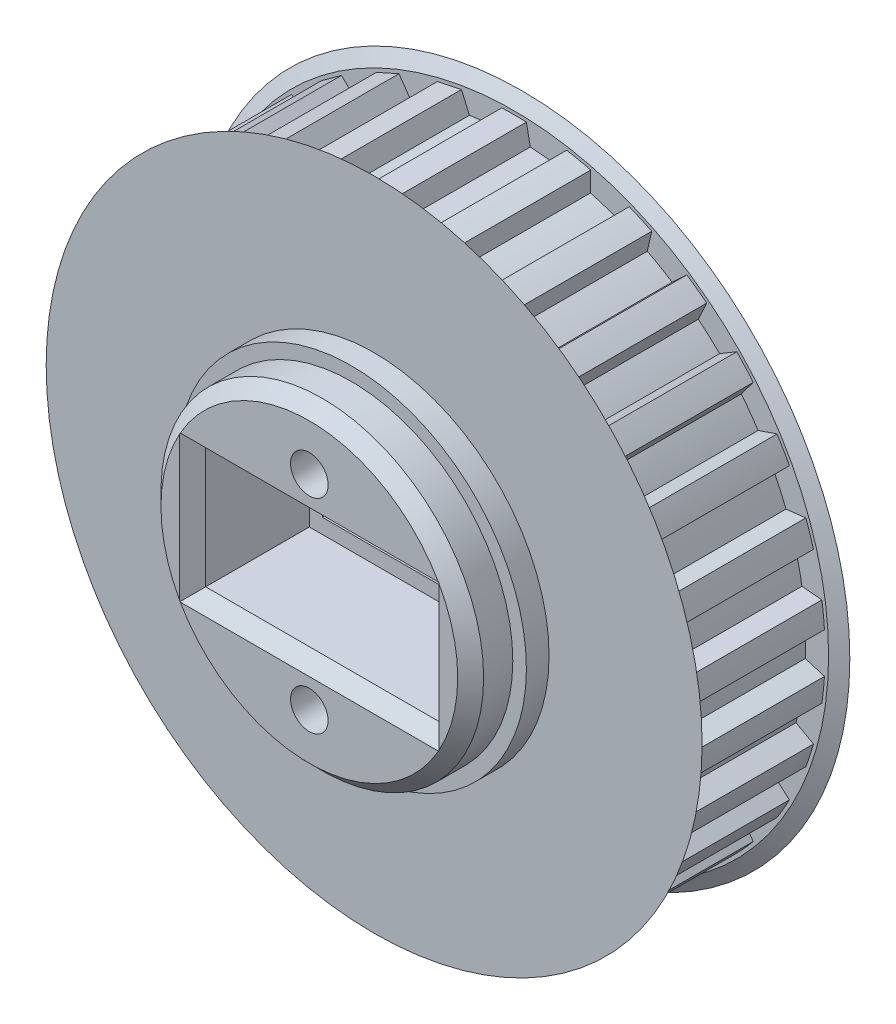
SolidWorks part; units mm, degrees
material "ABS"
ref_plane "Alzado" through (0, 0, 0) normal (0, 0, 1) x (1, 0, 0)
ref_plane "Planta" through (0, 0, 0) normal (0, 1, 0) x (1, 0, 0)
ref_plane "Vista lateral" through (0, 0, 0) normal (1, 0, 0) x (0, 0, -1)
sketch "Croquis1" plane through (0, 0, 0) normal (0, 0, 1) x (1, 0, 0)
  line L0 (0, 0) -> (0, 14.5885) construction
  line L1 (-0.95, 23.9812) -> (-1.25, 22.4653)
  line L2 (0.95, 23.9812) -> (1.25, 22.4653)
  line L3 (5.9152, 23.2596) -> (5.8935, 21.7144)
  line L4 (4.0567, 23.6547) -> (3.4481, 22.2342)
  line L5 (10.6219, 21.5215) -> (10.2794, 20.0146)
  line L6 (8.8862, 22.2943) -> (7.9955, 21.0314)
  line L7 (14.8644, 18.8428) -> (14.216, 17.44)
  line L8 (13.3272, 19.9596) -> (12.1935, 18.9095)
  line L9 (18.4572, 15.3406) -> (17.5313, 14.1033)
  line L10 (17.1858, 16.7525) -> (15.8585, 15.9611)
  line L11 (21.2433, 11.1679) -> (20.0805, 10.1501)
  line L12 (20.2933, 12.8133) -> (18.8305, 12.3152)
  line L13 (23.101, 6.5071) -> (21.752, 5.7533)
  line L14 (22.5139, 8.3141) -> (20.9795, 8.131)
  line L15 (23.9491, 1.5619) -> (22.4728, 1.1051)
  line L16 (23.7505, 3.4515) -> (22.2115, 3.5914)
  line L17 (23.7505, -3.4515) -> (22.2115, -3.5914)
  line L18 (23.9491, -1.5619) -> (22.4728, -1.1051)
  line L19 (22.5139, -8.3141) -> (20.9795, -8.131)
  line L20 (23.101, -6.5071) -> (21.752, -5.7533)
  line L21 (20.2933, -12.8133) -> (18.8305, -12.3152)
  line L22 (21.2433, -11.1679) -> (20.0805, -10.1501)
  line L23 (17.1858, -16.7525) -> (15.8585, -15.9611)
  line L24 (18.4572, -15.3406) -> (17.5313, -14.1033)
  line L25 (13.3272, -19.9596) -> (12.1935, -18.9095)
  line L26 (14.8644, -18.8428) -> (14.216, -17.44)
  line L27 (8.8862, -22.2943) -> (7.9955, -21.0314)
  line L28 (10.6219, -21.5215) -> (10.2794, -20.0146)
  line L29 (4.0567, -23.6547) -> (3.4481, -22.2342)
  line L30 (5.9152, -23.2596) -> (5.8935, -21.7144)
  line L31 (-0.95, -23.9812) -> (-1.25, -22.4653)
  line L32 (0.95, -23.9812) -> (1.25, -22.4653)
  line L33 (-5.9152, -23.2596) -> (-5.8935, -21.7144)
  line L34 (-4.0567, -23.6547) -> (-3.4481, -22.2342)
  line L35 (-10.6219, -21.5215) -> (-10.2794, -20.0146)
  line L36 (-8.8862, -22.2943) -> (-7.9955, -21.0314)
  line L37 (-14.8644, -18.8428) -> (-14.216, -17.44)
  line L38 (-13.3272, -19.9596) -> (-12.1935, -18.9095)
  line L39 (-18.4572, -15.3406) -> (-17.5313, -14.1033)
  line L40 (-17.1858, -16.7525) -> (-15.8585, -15.9611)
  line L41 (-21.2433, -11.1679) -> (-20.0805, -10.1501)
  line L42 (-20.2933, -12.8133) -> (-18.8305, -12.3152)
  line L43 (-23.101, -6.5071) -> (-21.752, -5.7533)
  line L44 (-22.5139, -8.3141) -> (-20.9795, -8.131)
  line L45 (-23.9491, -1.5619) -> (-22.4728, -1.1051)
  line L46 (-23.7505, -3.4515) -> (-22.2115, -3.5914)
  line L47 (-23.7505, 3.4515) -> (-22.2115, 3.5914)
  line L48 (-23.9491, 1.5619) -> (-22.4728, 1.1051)
  line L49 (-22.5139, 8.3141) -> (-20.9795, 8.131)
  line L50 (-23.101, 6.5071) -> (-21.752, 5.7533)
  line L51 (-20.2933, 12.8133) -> (-18.8305, 12.3152)
  line L52 (-21.2433, 11.1679) -> (-20.0805, 10.1501)
  line L53 (-17.1858, 16.7525) -> (-15.8585, 15.9611)
  line L54 (-18.4572, 15.3406) -> (-17.5313, 14.1033)
  line L55 (-13.3272, 19.9596) -> (-12.1935, 18.9095)
  line L56 (-14.8644, 18.8428) -> (-14.216, 17.44)
  line L57 (-18.4572, 15.3406) -> (-17.1858, 16.7525)
  line L58 (-14.8644, 18.8428) -> (-13.3272, 19.9596)
  line L59 (-8.8862, 22.2943) -> (-7.9955, 21.0314)
  line L60 (-10.6219, 21.5215) -> (-10.2794, 20.0146)
  line L61 (-4.0567, 23.6547) -> (-3.4481, 22.2342)
  line L62 (-5.9152, 23.2596) -> (-5.8935, 21.7144)
  line L63 (-10.6219, 21.5215) -> (-8.8862, 22.2943)
  line L64 (-5.9152, 23.2596) -> (-4.0567, 23.6547)
  arc A0 (-17.5313, 14.1033) -> (-18.8305, 12.3152) centre (0, 0) ccw
  arc A1 (3.4481, 22.2342) -> (1.25, 22.4653) centre (0, 0) ccw
  arc A2 (-14.216, 17.44) -> (-15.8585, 15.9611) centre (0, 0) ccw
  arc A3 (-5.8935, 21.7144) -> (-7.9955, 21.0314) centre (0, 0) ccw
  arc A4 (-10.2794, 20.0146) -> (-12.1935, 18.9095) centre (0, 0) ccw
  arc A8 (-20.2933, 12.8133) -> (-21.2433, 11.1679) centre (0, 0) ccw
  arc A9 (-22.5139, 8.3141) -> (-23.101, 6.5071) centre (0, 0) ccw
  arc A10 (-23.7505, 3.4515) -> (-23.9491, 1.5619) centre (0, 0) ccw
  arc A11 (5.9152, 23.2596) -> (4.0567, 23.6547) centre (0, 0) ccw
  arc A12 (0.95, 23.9812) -> (-0.95, 23.9812) centre (0, 0) ccw
  arc A16 (10.6219, 21.5215) -> (8.8862, 22.2943) centre (0, 0) ccw
  arc A17 (14.8644, 18.8428) -> (13.3272, 19.9596) centre (0, 0) ccw
  arc A18 (18.4572, 15.3406) -> (17.1858, 16.7525) centre (0, 0) ccw
  arc A19 (21.2433, 11.1679) -> (20.2933, 12.8133) centre (0, 0) ccw
  arc A20 (23.101, 6.5071) -> (22.5139, 8.3141) centre (0, 0) ccw
  arc A21 (23.9491, 1.5619) -> (23.7505, 3.4515) centre (0, 0) ccw
  arc A22 (23.7505, -3.4515) -> (23.9491, -1.5619) centre (0, 0) ccw
  arc A23 (22.5139, -8.3141) -> (23.101, -6.5071) centre (0, 0) ccw
  arc A24 (20.2933, -12.8133) -> (21.2433, -11.1679) centre (0, 0) ccw
  arc A25 (17.1858, -16.7525) -> (18.4572, -15.3406) centre (0, 0) ccw
  arc A26 (-0.95, -23.9812) -> (0.95, -23.9812) centre (0, 0) ccw
  arc A27 (-5.9152, -23.2596) -> (-4.0567, -23.6547) centre (0, 0) ccw
  arc A28 (-10.6219, -21.5215) -> (-8.8862, -22.2943) centre (0, 0) ccw
  arc A29 (-18.4572, -15.3406) -> (-17.1858, -16.7525) centre (0, 0) ccw
  arc A30 (-21.2433, -11.1679) -> (-20.2933, -12.8133) centre (0, 0) ccw
  arc A31 (-23.101, -6.5071) -> (-22.5139, -8.3141) centre (0, 0) ccw
  arc A32 (-23.9491, -1.5619) -> (-23.7505, -3.4515) centre (0, 0) ccw
  arc A33 (4.0567, -23.6547) -> (5.9152, -23.2596) centre (0, 0) ccw
  arc A34 (8.8862, -22.2943) -> (10.6219, -21.5215) centre (0, 0) ccw
  arc A35 (13.3272, -19.9596) -> (14.8644, -18.8428) centre (0, 0) ccw
  arc A36 (7.9955, 21.0314) -> (5.8935, 21.7144) centre (0, 0) ccw
  arc A37 (12.1935, 18.9095) -> (10.2794, 20.0146) centre (0, 0) ccw
  arc A39 (-1.25, 22.4653) -> (-3.4481, 22.2342) centre (0, 0) ccw
  arc A43 (15.8585, 15.9611) -> (14.216, 17.44) centre (0, 0) ccw
  arc A44 (18.8305, 12.3152) -> (17.5313, 14.1033) centre (0, 0) ccw
  arc A45 (20.9795, 8.131) -> (20.0805, 10.1501) centre (0, 0) ccw
  arc A46 (22.2115, 3.5914) -> (21.752, 5.7533) centre (0, 0) ccw
  arc A47 (22.4728, -1.1051) -> (22.4728, 1.1051) centre (0, 0) ccw
  arc A48 (21.752, -5.7533) -> (22.2115, -3.5914) centre (0, 0) ccw
  arc A49 (20.0805, -10.1501) -> (20.9795, -8.131) centre (0, 0) ccw
  arc A50 (17.5313, -14.1033) -> (18.8305, -12.3152) centre (0, 0) ccw
  arc A51 (14.216, -17.44) -> (15.8585, -15.9611) centre (0, 0) ccw
  arc A52 (10.2794, -20.0146) -> (12.1935, -18.9095) centre (0, 0) ccw
  arc A53 (5.8935, -21.7144) -> (7.9955, -21.0314) centre (0, 0) ccw
  arc A54 (1.25, -22.4653) -> (3.4481, -22.2342) centre (0, 0) ccw
  arc A55 (-3.4481, -22.2342) -> (-1.25, -22.4653) centre (0, 0) ccw
  arc A56 (-7.9955, -21.0314) -> (-5.8935, -21.7144) centre (0, 0) ccw
  arc A57 (-12.1935, -18.9095) -> (-10.2794, -20.0146) centre (0, 0) ccw
  arc A58 (-15.8585, -15.9611) -> (-14.216, -17.44) centre (0, 0) ccw
  arc A59 (-18.8305, -12.3152) -> (-17.5313, -14.1033) centre (0, 0) ccw
  arc A60 (-20.9795, -8.131) -> (-20.0805, -10.1501) centre (0, 0) ccw
  arc A61 (-22.2115, -3.5914) -> (-21.752, -5.7533) centre (0, 0) ccw
  arc A62 (-22.4728, 1.1051) -> (-22.4728, -1.1051) centre (0, 0) ccw
  arc A63 (-21.752, 5.7533) -> (-22.2115, 3.5914) centre (0, 0) ccw
  arc A64 (-20.0805, 10.1501) -> (-20.9795, 8.131) centre (0, 0) ccw
  arc A71 (-14.8644, -18.8428) -> (-13.3272, -19.9596) centre (0, 0) ccw
  circle A72 centre (0, 0) radius 1.5
  point P151 (0, 0)
  dimension "D1" = 24
  dimension "D6" = 3
  dimension "D5" = 1.5
  dimension "D2" = 2.5
  dimension "D3" = 1.9
  dimension "D4" = 30
extrude "Saliente-Extruir1" add sketch "Croquis1" along normal blind 10.2
sketch "Croquis2" plane through (0, 0, 10.2) normal (0, 0, 1) x (1, 0, 0)
  circle A0 centre (0, 0) radius 26
  circle A1 centre (0, 0) radius 1.5
  circle A2 centre (0, 0) radius 1.5 construction
  dimension "D1" = 52
extrude "Saliente-Extruir2" add sketch "Croquis2" along normal blind 0.6
sketch "Croquis3" plane through (0, 0, 10.8) normal (0, 0, 1) x (1, 0, 0)
  circle A0 centre (0, 0) radius 1.5
  circle A1 centre (0, 0) radius 12.45
  circle A3 centre (0, 0) radius 1.5 construction
  dimension "D1" = 24.9
sketch "Croquis4" plane through (0, 0, 0) normal (0, 0, -1) x (-1, 0, 0)
  circle A0 centre (0, 0) radius 1.5
  circle A1 centre (0, 0) radius 12.45
  circle A2 centre (0, 0) radius 1.5 construction
  dimension "D1" = 24.9
extrude "Saliente-Extruir4" add sketch "Croquis4" along normal blind 4.25
sketch "Croquis6" plane through (0, 0, 0) normal (0, 0, -1) x (-1, 0, 0)
  circle A0 centre (0, 0) radius 26
  circle A1 centre (0, 0) radius 1.5
  circle A2 centre (0, 0) radius 1.5 construction
  dimension "D1" = 52
extrude "Saliente-Extruir6" add sketch "Croquis6" along normal blind 0.6
sketch "Croquis5" plane through (0, 0, -0.6) normal (0, 0, -1) x (-1, 0, 0)
  circle A0 centre (0, 0) radius 1.5
  circle A1 centre (0, 0) radius 13.5
  circle A2 centre (0, 0) radius 1.5 construction
  dimension "D1" = 27
extrude "Saliente-Extruir5" add sketch "Croquis5" along normal blind 1.75
chamfer "Chaflán2" distance 1 angle 60 2 edges at (-26, 0, 0) (26, 0, 10.2)
extrude "Saliente-Extruir7" add sketch "Croquis3" along normal blind 5
chamfer "Chaflán4" distance 1 angle 45 1 edges at (12.45, 0, 15.8)
sketch "Croquis7" plane through (0, 0, 10.8) normal (0, 0, 1) x (1, 0, 0)
  circle A0 centre (0, 0) radius 1.5
  circle A1 centre (0, 0) radius 13.5
  circle A2 centre (0, 0) radius 1.5 construction
  dimension "D1" = 27
extrude "Saliente-Extruir8" add sketch "Croquis7" along normal blind 1.75
sketch "Croquis8" plane through (0, 0, 0) normal (0, 0, 1) x (1, 0, 0)
  line L0 (0, 0) -> (6.706, 0) construction
  line L1 (-8, 3.5) -> (8, 3.5)
  line L2 (-8, 3.5) -> (-8, -3.5)
  line L3 (-8, -3.5) -> (8, -3.5)
  line L4 (8, 3.5) -> (8, -3.5)
  line L5 (-8, 3.5) -> (8, -3.5) construction
  line L6 (-8, -3.5) -> (8, 3.5) construction
  circle A0 centre (0, 7.8756) radius 1.45
  circle A1 centre (0, -7.8756) radius 1.45
  point P0 (0, 0)
  dimension "D1" = 2.9
  dimension "D2" = 7
  dimension "D3" = 16
extrude "Cortar-Extruir1" cut sketch "Croquis8" against normal through all both and the other way through all
sketch "Croquis10" plane through (0, 0, 15.8) normal (0, 0, 1) x (1, 0, 0)
  line L1 (9, 4.65) -> (-9, 4.65)
  line L2 (9, 4.65) -> (9, -4.65)
  line L3 (9, -4.65) -> (-9, -4.65)
  line L4 (-9, 4.65) -> (-9, -4.65)
  line L5 (9, 4.65) -> (-9, -4.65) construction
  line L6 (9, -4.65) -> (-9, 4.65) construction
  point P0 (0, 0)
  dimension "D1" = 9.3
  dimension "D2" = 18
extrude "Cortar-Extruir3" cut sketch "Croquis10" against normal blind 9
chamfer "Chaflán5" distance 1 angle 45 8 edges at (-8, 0, -4.25) (0, 3.5, -4.25) (8, 0, -4.25) (0, -3.5, -4.25) (9, 0, 15.8) (0, 4.65, 15.8) (-9, 0, 15.8) (0, -4.65, 15.8)
sketch "Sketch1" plane through (0, 0, -4.25) normal (0, 0, -1) x (-1, 0, 0)
  circle A0 centre (0, 0) radius 12.45
  circle A1 centre (0, 0) radius 12.45 construction
  circle A2 centre (0, 7.8756) radius 1.45
  circle A3 centre (0, -7.8756) radius 1.45
  circle A4 centre (0, 7.8756) radius 1.45 construction
extrude "Boss-Extrude1" add sketch "Sketch1" against normal blind 5
sketch "Sketch2" plane through (0, 0, -4.25) normal (0, 0, -1) x (-1, 0, 0)
  line L0 (0, 17.274) -> (0, -20.0751) construction
  line L1 (-7.5, 0) -> (7.5, 0) construction
  circle A0 centre (-7.5, 0) radius 1.45
  circle A1 centre (7.5, 0) radius 1.45
  point P7 (7.5, 1.8828)
  dimension "D1" = 2.9
  dimension "D2" = 15
extrude "Cut-Extrude1" cut sketch "Sketch2" against normal through all
sketch "Sketch4" plane through (0, 0, 15.8) normal (0, 0, 1) x (1, 0, 0)
  line L0 (-8, -3.5) -> (8, -3.5) construction
  line L1 (4, 3.5) -> (-4, 3.5)
  line L2 (4, 3.5) -> (4, -3.5)
  line L3 (4, -3.5) -> (-4, -3.5)
  line L4 (-4, 3.5) -> (-4, -3.5)
  line L5 (4, 3.5) -> (-4, -3.5) construction
  line L6 (4, -3.5) -> (-4, 3.5) construction
  point P0 (0, 0)
  dimension "D1" = 8
extrude "Cut-Extrude2" cut sketch "Sketch4" against normal blind 21
chamfer "Chamfer3" distance 1 angle 45 4 edges at (-4, 0, -4.25) (0, 3.5, -4.25) (4, 0, -4.25) (0, -3.5, -4.25)
chamfer "Chamfer2" distance 0.75 angle 45 1 edges at (-12.45, 0, -4.25)
